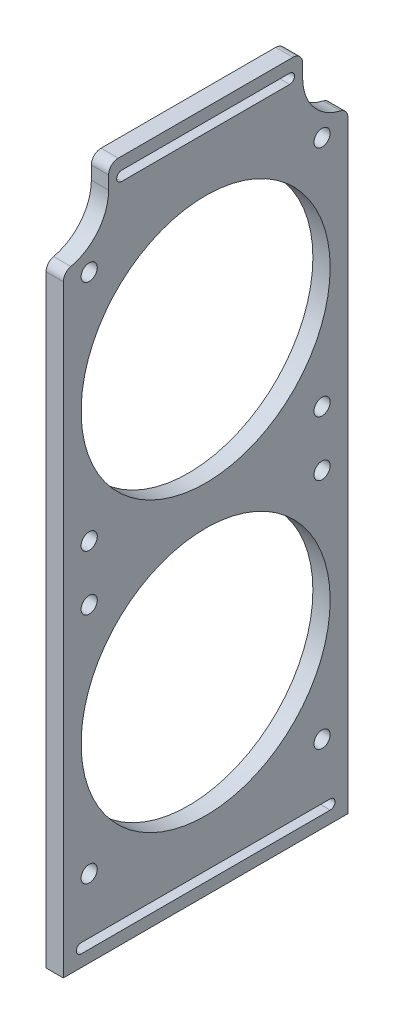
SolidWorks part; units mm, degrees
ref_plane "Front Plane" through (0, 0, 0) normal (0, 0, 1) x (1, 0, 0)
ref_plane "Top Plane" through (0, 0, 0) normal (0, 1, 0) x (1, 0, 0)
ref_plane "Right Plane" through (0, 0, 0) normal (1, 0, 0) x (0, 0, -1)
sketch "Sketch2" plane through (0, 0, 0) normal (1, 0, 0) x (0, 0, -1)
  line L0 (-41.5091, 5.3238) -> (38.4909, 5.3238) construction
  line L1 (-41.5091, 94.3907) -> (38.4909, 94.3907) construction
  line L2 (-41.5091, 94.3907) -> (-41.5091, 14.3907) construction
  line L3 (-41.5091, 14.3907) -> (38.4909, 14.3907) construction
  line L4 (38.4909, 94.3907) -> (38.4909, 14.3907) construction
  line L5 (-41.5091, 94.3907) -> (38.4909, 14.3907) construction
  line L6 (-41.5091, 14.3907) -> (38.4909, 94.3907) construction
  line L7 (-41.5091, 5.3238) -> (-41.5091, -74.6762) construction
  line L8 (-41.5091, -74.6762) -> (38.4909, -74.6762) construction
  line L9 (38.4909, 5.3238) -> (38.4909, -74.6762) construction
  line L10 (-41.5091, 5.3238) -> (38.4909, -74.6762) construction
  line L11 (-41.5091, -74.6762) -> (38.4909, 5.3238) construction
  line L12 (-37.5091, 1.3238) -> (34.4909, 1.3238) construction
  line L13 (-37.5091, 1.3238) -> (-37.5091, -70.6762) construction
  line L14 (-37.5091, -70.6762) -> (34.4909, -70.6762) construction
  line L15 (34.4909, 1.3238) -> (34.4909, -70.6762) construction
  line L16 (-37.5091, 1.3238) -> (34.4909, -70.6762) construction
  line L17 (-37.5091, -70.6762) -> (34.4909, 1.3238) construction
  line L18 (-37.5091, 90.3907) -> (34.4909, 90.3907) construction
  line L19 (-37.5091, 90.3907) -> (-37.5091, 18.3907) construction
  line L20 (-37.5091, 18.3907) -> (34.4909, 18.3907) construction
  line L21 (34.4909, 90.3907) -> (34.4909, 18.3907) construction
  line L22 (-37.5091, 90.3907) -> (34.4909, 18.3907) construction
  line L23 (-37.5091, 18.3907) -> (34.4909, 90.3907) construction
  line L24 (38.4909, -94.6179) -> (-41.5091, -94.6179)
  line L25 (38.4909, -94.6179) -> (38.4909, 94.3907)
  line L26 (38.4909, 94.3907) -> (28.4909, 94.3907)
  line L27 (-41.5091, -94.6179) -> (-41.5091, 94.3907)
  line L28 (38.4909, -94.6179) -> (-41.5091, 94.3907) construction
  line L29 (38.4909, 94.3907) -> (-41.5091, -94.6179) construction
  line L30 (-31.5091, 94.3907) -> (-41.5091, 94.3907)
  line L31 (-31.5091, 116.4166) -> (28.4909, 116.4166)
  line L32 (-31.5091, 116.4166) -> (-31.5091, 94.3907)
  line L33 (-45.5091, -94.6179) -> (-45.5091, 94.3907)
  line L34 (28.4909, 116.4166) -> (28.4909, 94.3907)
  line L35 (-31.5091, 116.4166) -> (28.4909, 94.3907) construction
  line L36 (-31.5091, 94.3907) -> (28.4909, 116.4166) construction
  line L37 (42.4909, -94.6179) -> (42.4909, 94.3907)
  line L38 (-45.5091, -94.6179) -> (-41.5091, -94.6179)
  line L39 (38.4909, -94.6179) -> (42.4909, -94.6179)
  line L40 (38.4909, 94.3907) -> (42.4909, 94.3907)
  line L41 (-45.5091, 94.3907) -> (-41.5091, 94.3907)
  circle A0 centre (-1.5091, -34.6762) radius 38.5
  circle A1 centre (-1.5091, 54.3907) radius 38.5
  point P0 (-1.5091, 54.3907)
  point P5 (-1.5091, -34.6762)
  point P9 (-1.5091, -34.6762)
  point P15 (-1.5091, 54.3907)
  point P22 (-1.5091, -0.1136)
  point P27 (-1.5091, 105.4037)
  point P32 (-1.5091, 111.1537)
  point P33 (-1.4929, -89.4156)
  dimension "D5" = 77
  dimension "D6" = 77
  dimension "D1" = 80
  dimension "D2" = 80
  dimension "D3" = 72
  dimension "D4" = 72
  dimension "D7" = 60
  dimension "D8" = 5.75
extrude "Boss-Extrude2" add sketch "Sketch2" along normal blind 5.334 contours L34 L31 L32 L30 L27 L24 L25 L26 A1 A0 | L41 L33 L38 L27 | L40 L25 L39 L37 region at (0, 6.421, 1.5091) region at (0, -0.1136, -40.4909) region at (0, -0.1136, 43.5091)
hole_wizard "Ø3.0mm Dowel Slot1" positions "Sketch3" profile "Sketch4" size "Ø3.0" standard "ANSI Metric" slot yes end condition through all
sketch "Sketch3" plane through (0, 0, 0) normal (-1, 0, 0) x (0, 0, 1)
  line L0 (-38.5071, -89.4156) -> (41.4929, -89.4156) construction
  point P0 (1.4929, -89.4156)
  dimension "D1" = 80
sketch "Sketch4" plane through (0, -89.4156, 1.4929) normal (0, 1, 0) x (0, 0, 1)
  line L0 (0, 0) -> (0, 5.334)
  line L1 (0, 5.334) -> (1.5, 5.334)
  line L2 (1.5, 5.334) -> (1.5, 0)
  line L5 (1.5, 0) -> (0, 0)
  line L11 (0, -6.35) -> (0, 107.95) construction
  dimension "Thru Hole Dia." = 3
  dimension "Thru Hole Depth" = 5.334
hole_wizard "Ø3.0mm Dowel Slot2" positions "Sketch5" profile "Sketch6" size "Ø3.0" standard "ANSI Metric" slot yes end condition through all
sketch "Sketch5" plane through (0, 0, 0) normal (-1, 0, 0) x (0, 0, 1)
  line L0 (-25.9909, 111.1537) -> (29.0091, 111.1537) construction
  point P0 (1.5091, 111.1537)
  dimension "D1" = 55
sketch "Sketch6" plane through (0, 111.1537, 1.5091) normal (0, 1, 0) x (0, 0, 1)
  line L0 (0, 0) -> (0, 5.334)
  line L1 (0, 5.334) -> (1.5, 5.334)
  line L2 (1.5, 5.334) -> (1.5, 0)
  line L5 (1.5, 0) -> (0, 0)
  line L11 (0, -6.35) -> (0, 107.95) construction
  dimension "Thru Hole Dia." = 3
  dimension "Thru Hole Depth" = 5.334
fillet "Fillet1" radius 15 2 edges at (2.667, 94.3907, 31.5091) (2.667, 94.3907, -28.4909)
fillet "Fillet2" radius 3 4 edges at (2.667, 94.3907, 45.5091) (2.667, 116.4166, 31.5091) (2.667, 116.4166, -28.4909) (2.667, 94.3907, -42.4909)
hole_wizard "Ø5.0mm Dowel Hole1" positions "Sketch7" profile "Sketch8" hole size "Ø5.0" standard "ANSI Metric" end condition through all
sketch "Sketch7" plane through (0, 0, 0) normal (-1, 0, 0) x (0, 0, 1)
  point P0 (-34.4909, 90.3907)
  point P3 (37.5091, 90.3907)
  point P6 (-34.4909, 18.3907)
  point P9 (37.5091, 18.3907)
  point P12 (37.5091, 1.3238)
  point P15 (-34.4909, 1.3238)
  point P18 (-34.4909, -70.6762)
  point P21 (37.5091, -70.6762)
sketch "Sketch8" plane through (0, 90.3907, -34.4909) normal (0, 1, 0) x (0, 0, 1)
  line L0 (0, 0) -> (0, 5.334)
  line L1 (0, 5.334) -> (2.5, 5.334)
  line L2 (2.5, 5.334) -> (2.5, 0)
  line L5 (2.5, 0) -> (0, 0)
  line L11 (0, -6.35) -> (0, 107.95) construction
  dimension "Thru Hole Dia." = 5
  dimension "Thru Hole Depth" = 5.334
